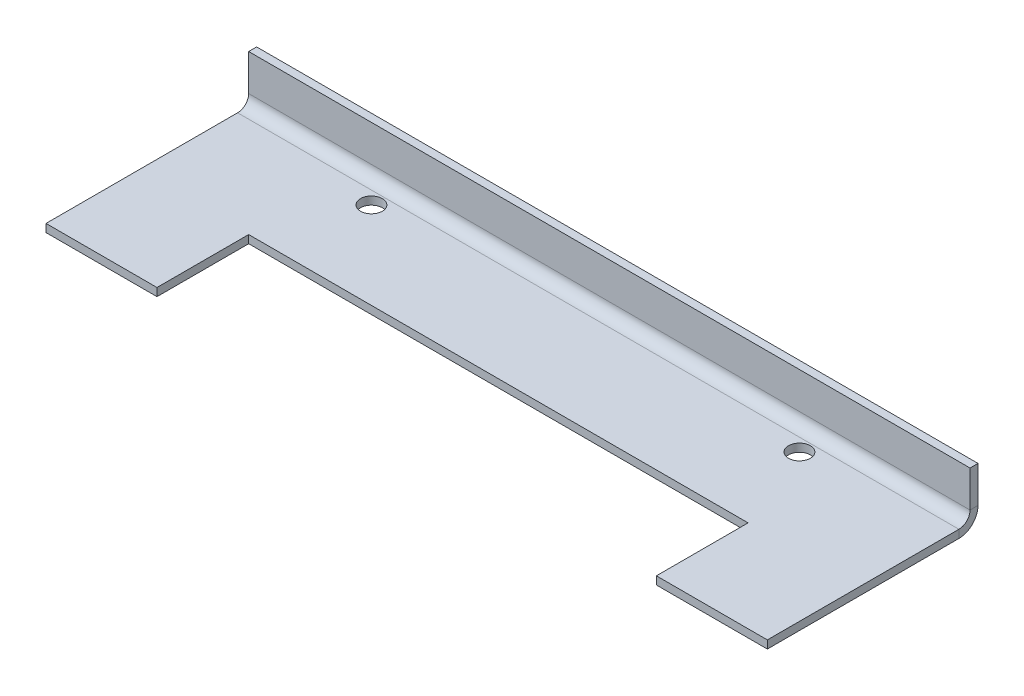
SolidWorks part; units mm, degrees
note: The reader was unsure of these and kept them because the rebuilt part matched: flange length of "Edge-Flange1".
material "1060 Alloy"
ref_plane "Front" through (0, 0, 0) normal (0, 0, 1) x (1, 0, 0)
ref_plane "Top" through (0, 0, 0) normal (0, 1, 0) x (1, 0, 0)
ref_plane "Right" through (0, 0, 0) normal (1, 0, 0) x (0, 0, -1)
sketch "Sketch1" plane through (0, 0, 0) normal (0, 1, 0) x (1, 0, 0)
  line L0 (0, -24.8246) -> (0, -48.0188)
  line L1 (12.7, -37.5246) -> (69.85, -37.5246)
  line L3 (0, -24.8246) -> (82.55, -24.8246)
  line L6 (82.55, -24.8246) -> (82.55, -48.0188)
  line L7 (82.55, -48.0188) -> (69.85, -48.0188)
  line L8 (69.85, -37.5246) -> (69.85, -48.0188)
  line L11 (0, -48.0188) -> (12.7, -48.0188)
  line L12 (12.7, -37.5246) -> (12.7, -48.0188)
  line L14 (12.7283, -48.0188) -> (0.0283, -48.0188) construction
  line L16 (12.7283, -26.0946) -> (0.0283, -26.0946) construction
  dimension "D1" = 82.55
  dimension "D2" = 12.7
  dimension "D3" = 12.7
  dimension "D4" = 1.27
base flange "Base-Flange1" sketch "Sketch1" thickness 0.9119 reverse thickness direction no parameters "D1"=1.27
hole_wizard "Ø2.5mm Dowel Hole1" positions "Sketch10" profile "Sketch11" hole size "Ø2.5" standard "ANSI Metric" end condition up to next
sketch "Sketch10" plane through (0, -0.9119, 0) normal (0, -1, 0) x (-1, 0, 0)
  line L0 (-12.7, -37.5246) -> (-69.85, -37.5246) construction
  line L1 (-65.7631, -27.5621) -> (-16.7869, -27.5621) construction
  line L3 (-41.275, -37.5246) -> (-41.275, -24.8246) construction
  line L4 (-82.55, -24.8246) -> (0, -24.8246) construction
  circle A4 centre (-16.7869, -27.5621) radius 1.3741 construction
  point P0 (-65.7631, -27.5621)
  point P2 (-16.7869, -27.5621)
  point P23 (-41.275, -27.5621)
sketch "Sketch11" plane through (65.7631, -0.9119, 27.5621) normal (1, 0, 0) x (0, 0, -1)
  line L0 (0, 0) -> (0, 0.9119)
  line L1 (0, 0.9119) -> (1.25, 0.9119)
  line L2 (1.25, 0.9119) -> (1.25, 0)
  line L5 (1.25, 0) -> (0, 0)
  line L11 (0, -6.35) -> (0, 107.95) construction
  dimension "Thru Hole Dia." = 2.5
  dimension "Thru Hole Depth" = 0.9119
edge flange "Edge-Flange1" sketch "Sketch14" flange angle 90 flange length 6.35 flange position material outside bend radius 1.27 thickness 0.9119 relief rectangular parameters "D6"=10
sketch "Sketch14" plane through (0, 0, 24.8246) normal (0, 0, -1) x (-1, 0, 0)
  line L2 (-82.55, 0) -> (-82.55, 5.4381)
  line L3 (-82.55, 5.4381) -> (0, 5.4381)
  line L4 (0, 5.4381) -> (0, 0)
  line L5 (-82.55, 0) -> (0, 0) construction
  line L6 (-82.55, 0) -> (0, 0)
bend "EdgeBend1" bend radius 1.27 bend angle 90 parameters "D5"=1
sketch "Bend-Lines1" [suppressed] plane through (0, 0, 0) normal (0, 1, 0) x (1, 0, 0)
sketch "Bounding-Box1" [suppressed] plane through (0, 0, 0) normal (0, 1, 0) x (1, 0, 0)
sheet metal parameters "Sheet-Metal1" thickness 0.9119 parameters "D1"=1.27
flat pattern "Flat-Pattern1" [suppressed]
sketch "Bend-Lines2" plane through (0, 0, 0) normal (0, 1, 0) x (1, 0, 0)
  line L0 (0, 6.7803) -> (82.55, 6.7803) construction
  line L1 (0, 6.7803) -> (82.55, 6.7803) construction
sketch3d "Bounding-Box2" [suppressed]
  line L0 (82.55, 19.05, 0) -> (0, 19.05, 0) construction
  line L1 (82.55, 0, 0) -> (0, 0, 0) construction
  line L2 (82.55, 19.05, 0) -> (82.55, 0, 0) construction
  line L3 (0, 19.05, 0) -> (0, 0, 0) construction
sheet metal parameters "Sheet-Metal2" thickness 0.9119 parameters "D1"=1.27
flat pattern "Flat-Pattern1"
sketch "Bend-Lines2" plane through (0, 0, 0) normal (0, 1, 0) x (1, 0, 0)
sketch3d "Bounding-Box2" [suppressed]
  line L0 (82.55, 0, 0) -> (0, 0, 0) construction
  line L1 (82.55, -19.05, 0) -> (0, -19.05, 0) construction
  line L2 (82.55, 0, 0) -> (82.55, -19.05, 0) construction
  line L3 (0, 0, 0) -> (0, -19.05, 0) construction
sheet metal parameters "Sheet-Metal3" thickness 0.9119 parameters "D1"=1.27
flat pattern "Flat-Pattern1"
sketch "Bend-Lines2" plane through (0, 0, 0) normal (0, 1, 0) x (1, 0, 0)
  line L0 (82.55, -24.7391) -> (0, -24.7391) construction
  line L1 (82.55, -24.7391) -> (0, -24.7391) construction
sketch3d "Bounding-Box2" [suppressed]
  line L0 (82.55, -19.2154, 0) -> (0, -19.2154, 0) construction
  line L1 (82.55, -48.0188, 0) -> (0, -48.0188, 0) construction
  line L2 (82.55, -19.2154, 0) -> (82.55, -48.0188, 0) construction
  line L3 (0, -19.2154, 0) -> (0, -48.0188, 0) construction
bend of the flat pattern "Flatten-<EdgeBend1>1"
